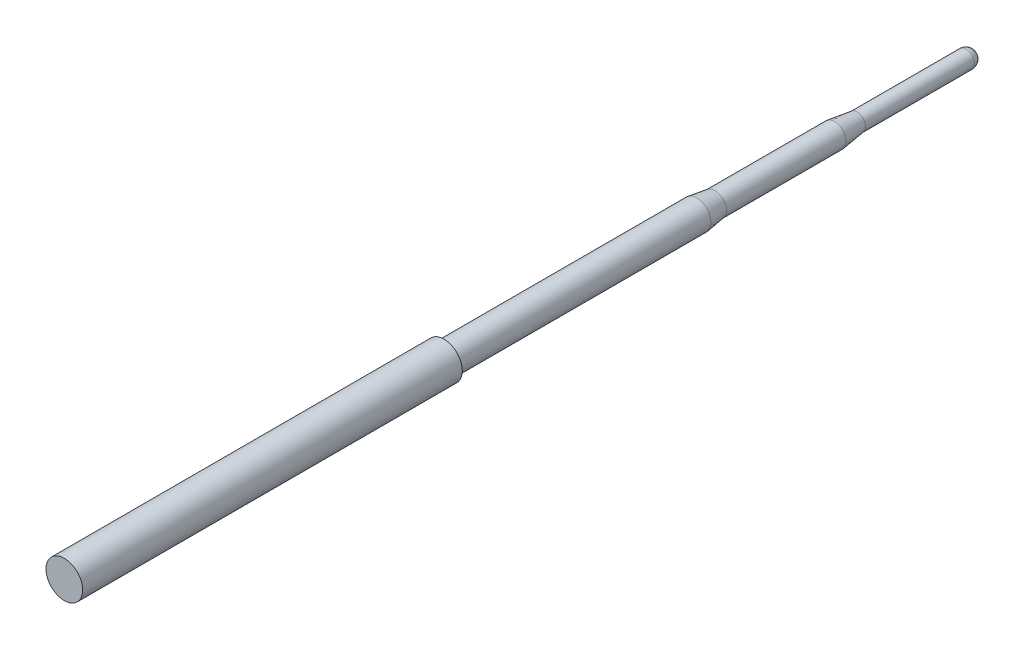
SolidWorks part; units mm, degrees
ref_plane "Front Plane" through (0, 0, 0) normal (0, 0, 1) x (1, 0, 0)
ref_plane "Top Plane" through (0, 0, 0) normal (0, 1, 0) x (1, 0, 0)
ref_plane "Right Plane" through (0, 0, 0) normal (1, 0, 0) x (0, 0, -1)
sketch "Sketch1" plane through (0, 0, 0) normal (-1, 0, 0) x (0, 1, 0)
  line L0 (-4.7879, -90.0618) -> (-3.8989, -83.9539)
  line L1 (-4.7879, -174.593) -> (-4.7879, -90.0618)
  line L2 (-2.8702, -36.3982) -> (-3.8989, -43.9997)
  line L3 (-4.7879, -174.593) -> (-6.1341, -174.593)
  line L4 (0, 0) -> (0, -301.593)
  line L5 (-3.8989, -83.9539) -> (-3.8989, -43.9997)
  line L6 (-6.1341, -174.593) -> (-6.1341, -301.593)
  line L7 (0, -301.593) -> (-6.1341, -301.593)
  line L8 (-2.8702, -36.3982) -> (-2.8702, 0)
  line L9 (-2.8702, 0) -> (0, 0)
  dimension "D1" = 4.7879
  dimension "D2" = 39.9542
  dimension "D3" = 36.3982
  dimension "D4" = 84.5312
  dimension "D5" = 6.1722
  dimension "D6" = 1.3462
  dimension "D7" = 127
  dimension "D8" = 2.8702
  dimension "D9" = 7.6708
  dimension "D10" = 3.8989
revolve "Revolve1" add sketch "Sketch1" angle 360 about L4
sketch "Sketch3" plane through (0, 0, 0) normal (0, 0, -1) x (0, -1, 0)
  circle A0 centre (0, 0) radius 2.8702
extrude "Boss-Extrude1" add sketch "Sketch3" along normal blind 2.8702
fillet "Fillet1" radius 2.8702 1 edges at (0, 2.8702, -2.8702)
